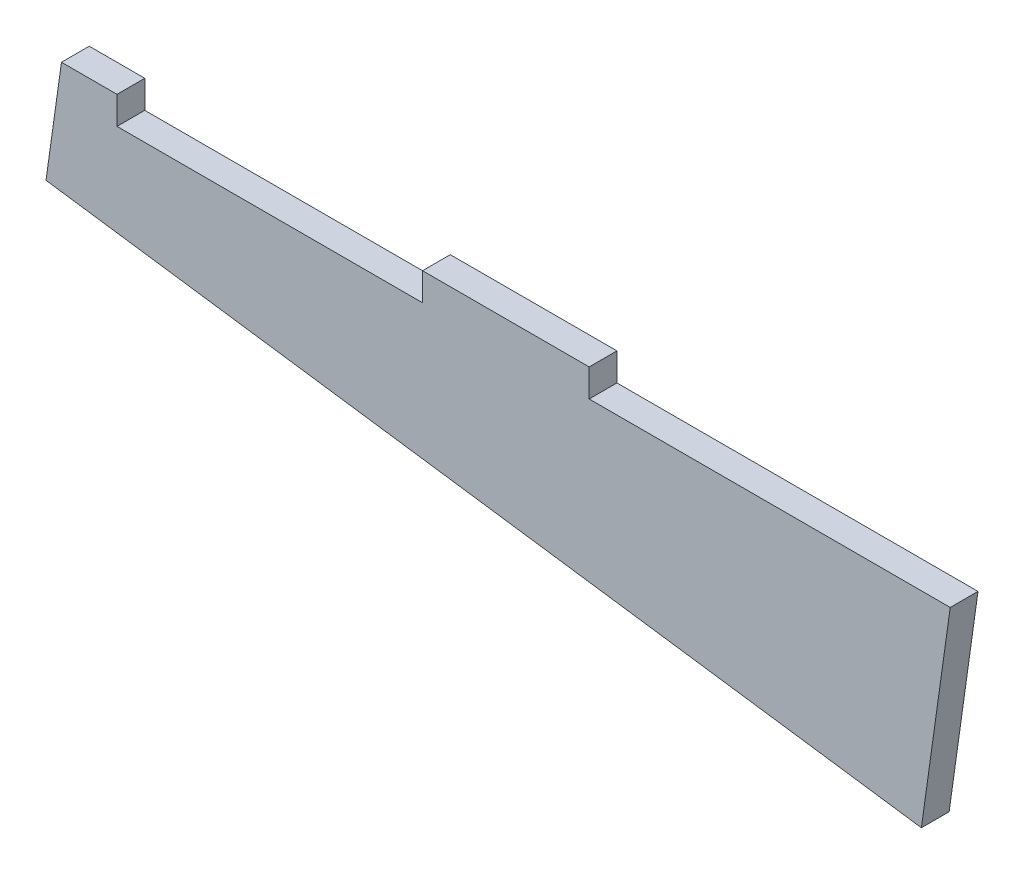
SolidWorks part; units mm, degrees
ref_plane "Front Plane" through (0, 0, 0) normal (0, 0, 1) x (1, 0, 0)
ref_plane "Top Plane" through (0, 0, 0) normal (0, 1, 0) x (1, 0, 0)
ref_plane "Right Plane" through (0, 0, 0) normal (1, 0, 0) x (0, 0, -1)
sketch "Sketch1" plane through (0, 0, 0) normal (0, 0, 1) x (1, 0, 0)
  line L0 (-194.0664, -59.2629) -> (-181.3664, -59.2629)
  line L4 (-181.3664, -59.2629) -> (-181.3664, -65.6129)
  line L5 (-181.3664, -65.6129) -> (-111.5164, -65.6129)
  line L6 (-111.5164, -65.6129) -> (-111.5164, -59.2629)
  line L7 (-111.5164, -59.2629) -> (-73.4164, -59.2629)
  line L8 (-73.4164, -59.2629) -> (-73.4164, -65.6129)
  line L9 (-73.4164, -65.6129) -> (9.1336, -65.6129)
  line L10 (9.1336, -65.6129) -> (2.5379, -112.5435)
  line L11 (2.5379, -112.5435) -> (-197.6014, -84.4157)
  line L12 (-197.6014, -84.4157) -> (-194.0664, -59.2629)
  line L13 (-955.1327, 116.7619) -> (-561.4327, 61.431) construction
  point P2 (-62.7286, -30.0583)
  dimension "D1" = 12.7
  dimension "D2" = 6.35
  dimension "D3" = 69.85
  dimension "D4" = 38.1
  dimension "D5" = 82.55
  dimension "D6" = 25.4
extrude "Boss-Extrude1" add sketch "Sketch1" against normal blind 6.35
